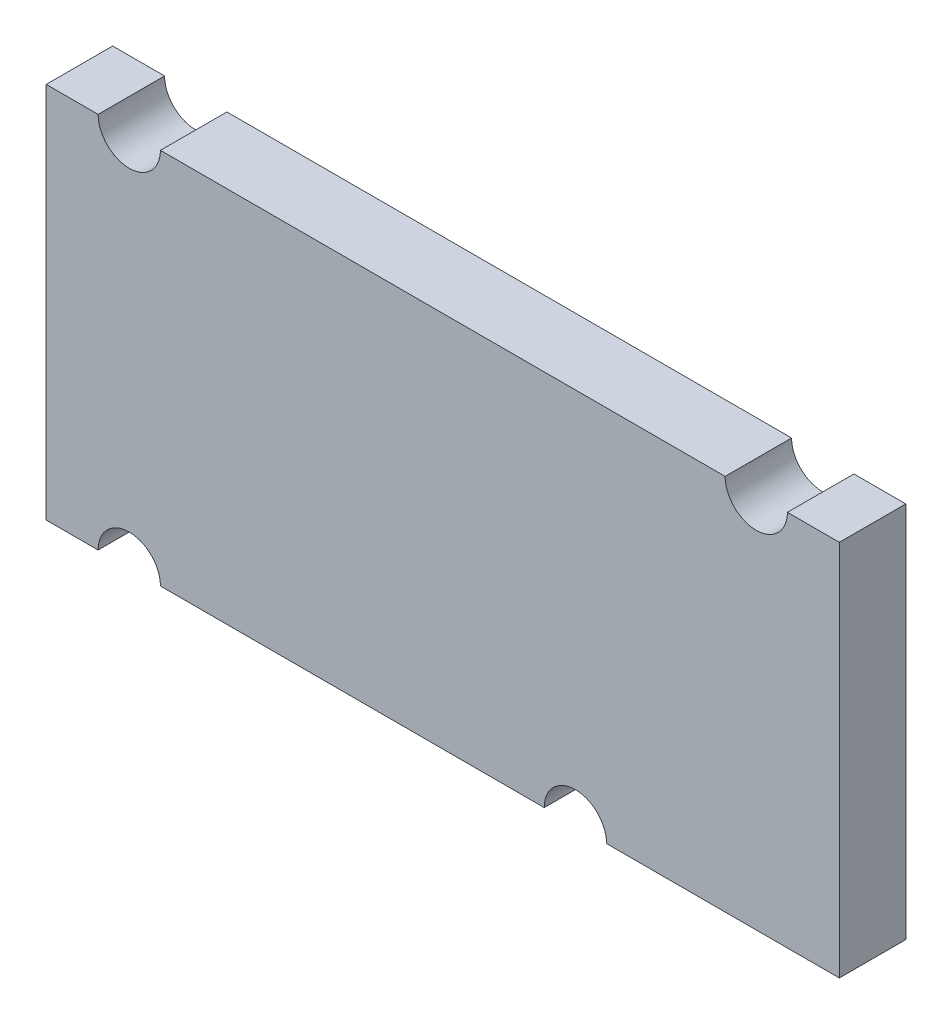
SolidWorks part; units mm, degrees
ref_plane "前视基准面" through (0, 0, 0) normal (0, 0, 1) x (1, 0, 0)
ref_plane "上视基准面" through (0, 0, 0) normal (0, 1, 0) x (1, 0, 0)
ref_plane "右视基准面" through (0, 0, 0) normal (1, 0, 0) x (0, 0, -1)
other "Configuration Table"
sketch "草图1" plane through (0, 0, 0) normal (0, 0, 1) x (1, 0, 0)
  line L0 (27.6219, -11.5) -> (27.6219, 12.73) construction
  line L1 (-20.1147, 11.355) -> (27.6219, 11.355)
  line L2 (-20.1147, 11.355) -> (-20.1147, -11.355)
  line L3 (-20.1147, -11.355) -> (27.6219, -11.355)
  line L4 (27.6219, 11.355) -> (27.6219, -11.355)
  line L5 (-20.1147, 12.73) -> (-20.1147, -12.73) construction
  line L9 (-16.9897, -11.355) -> (-16.9897, -13.23)
  line L10 (-16.9897, -11.355) -> (-16.9897, -13.23)
  line L11 (-16.9897, -13.23) -> (-13.2397, -13.23)
  line L12 (-16.9897, -13.23) -> (-13.2397, -13.23)
  line L13 (-13.2397, -13.23) -> (-13.2397, -11.355)
  line L14 (-13.2397, -13.23) -> (-13.2397, -11.355)
  arc A24 (-16.9897, 11.355) -> (-13.2397, 11.355) centre (-15.1147, 11.355) ccw
  circle A25 centre (-15.1147, 11.355) radius 1.875
  arc A27 (20.7469, 11.355) -> (24.4969, 11.355) centre (22.6219, 11.355) ccw
  circle A28 centre (22.6219, 11.355) radius 1.875
  arc A30 (-13.2397, -11.355) -> (-16.9897, -11.355) centre (-15.1147, -11.355) ccw
  arc A31 (-13.2397, -11.355) -> (-16.9897, -11.355) centre (-15.1147, -11.355) ccw
  arc A33 (13.6103, -11.355) -> (9.8603, -11.355) centre (11.7353, -11.355) ccw
  circle A34 centre (11.7353, -11.355) radius 1.875
  dimension "D1" = 0.5
  dimension "D2" = 0.5
  dimension "D3" = 0.5
  dimension "D4" = 0.5
extrude "凸台-拉伸1" add sketch "草图1" along normal blind 4 contours A34 L3 L4 L1 A28 A25 L2 A31 region at (3.8102, 0, 0)
